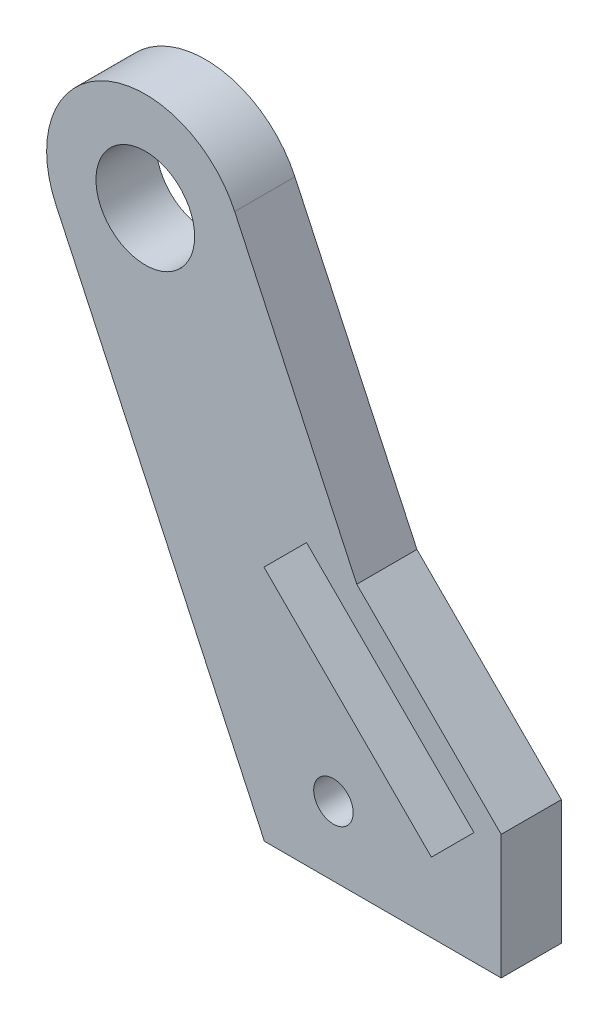
SolidWorks part; units mm, degrees
ref_plane "Front Plane" through (0, 0, 0) normal (0, 0, 1) x (1, 0, 0)
ref_plane "Top Plane" through (0, 0, 0) normal (0, 1, 0) x (1, 0, 0)
ref_plane "Right Plane" through (0, 0, 0) normal (1, 0, 0) x (0, 0, -1)
sketch "Sketch1" plane through (0, 0, 0) normal (0, 0, 1) x (1, 0, 0)
  line L0 (0, 12) -> (12, 0)
  line L1 (0, 0) -> (12, 0)
  line L2 (0, 0) -> (0, 12)
  line L3 (0, 12) -> (12, 12)
  line L4 (12, 0) -> (12, 12)
  line L5 (0, 0) -> (3.5, 0)
  line L6 (0, 0) -> (0, 3.5)
  line L7 (0, 3.5) -> (3.5, 3.5)
  line L8 (3.5, 0) -> (3.5, 3.5)
  line L9 (12, 0) -> (8.4645, 3.5355)
  line L10 (8.4645, 3.5355) -> (-0.0208, 12.0208)
  line L11 (-0.0208, 12.0208) -> (2.1359, 14.1775)
  line L12 (8.4645, 3.5355) -> (10.6211, 5.6922)
  line L13 (2.1359, 14.1775) -> (10.6211, 5.6922)
  line L14 (0, 0) -> (-10.5655, 22.6577)
  line L15 (-10.5655, 22.6577) -> (-1.5024, 26.8839)
  line L16 (-1.5024, 26.8839) -> (4.6816, 13.6223)
  line L17 (4.6816, 13.6223) -> (12, 6.3039)
  circle A0 centre (3.5, 3.5) radius 1
  circle A1 centre (-6.0339, 24.7708) radius 2.5
  circle A3 centre (-6.0339, 24.7708) radius 5
  point P16 (0, 0)
  point P21 (12, 6.6018)
  point P22 (12, 6.4525)
  point P23 (12, 6.3039)
  dimension "D5" = 2
  dimension "D6" = 5
  dimension "D7" = 10
  dimension "D1" = 12
  dimension "D2" = 12
  dimension "D3" = 3.5
  dimension "D4" = 3.5
extrude "Boss-Extrude1" add sketch "Sketch1" along normal blind 3.05 contours L15 A3 A1 | L15 A3 A1 | A3 L14 L2 L10 L11 L13 L3 L17 L16 | L17 L3 L13 L12 L0 L4 | A0 L8 L1 L0 L2 L7 | A0 L7 L2 L1 L8 region at (4.495, 4.495, 0) region at (-1.9729, 14.6273, 0) region at (9.6436, 4.5131, 0) region at (1.6592, 1.6592, 0) region at (-8.0967, 29.1945, 0) region at (-9.3823, 23.0782, 0)
